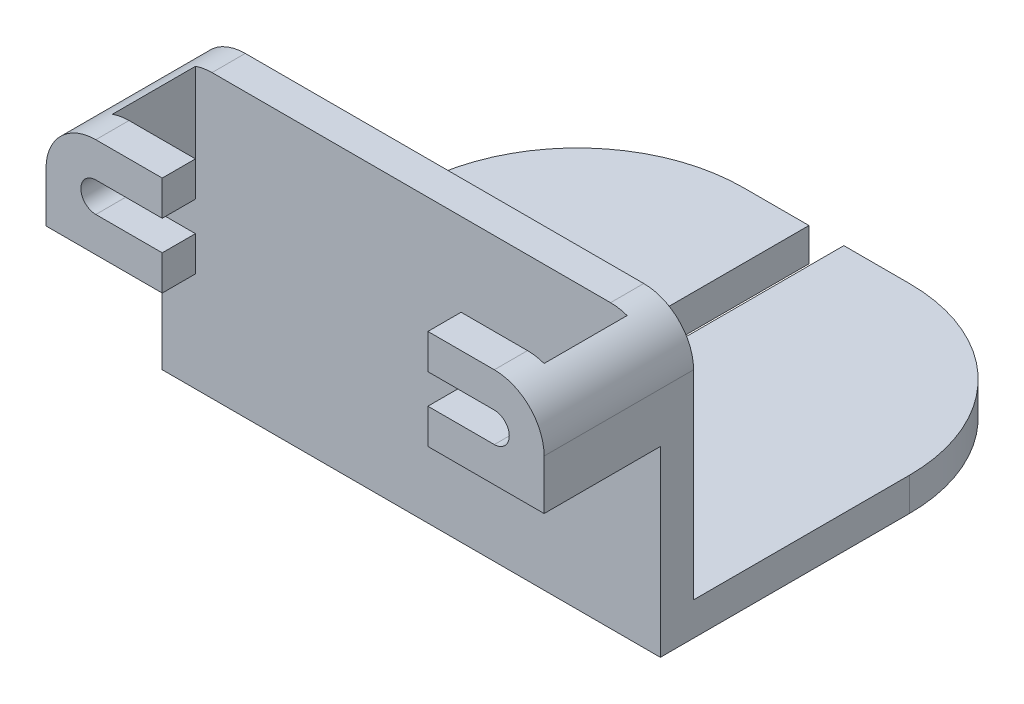
SolidWorks part; units mm, degrees
ref_plane "前视基准面" through (0, 0, 0) normal (0, 0, 1) x (1, 0, 0)
ref_plane "上视基准面" through (0, 0, 0) normal (0, 1, 0) x (1, 0, 0)
ref_plane "右视基准面" through (0, 0, 0) normal (1, 0, 0) x (0, 0, -1)
other "Configuration Table"
sketch "草图1" plane through (0, 0, 0) normal (1, 0, 0) x (0, 0, -1)
  line L1 (0, 0) -> (25, 0)
  line L2 (0, 0) -> (0, 17)
  line L3 (0, 17) -> (2, 17)
  line L4 (25, 0) -> (25, 2)
  line L8 (25, 2) -> (2, 2)
  line L9 (2, 17) -> (2, 2)
  dimension "D1" = 2
  dimension "D2" = 2
  dimension "D3" = 25
  dimension "D4" = 15
extrude "凸台-拉伸1" add sketch "草图1" along normal blind 30
sketch "草图3" plane through (0, 17, 0) normal (0, 1, 0) x (1, 0, 0)
  line L0 (15, 0) -> (15, 9.3774) construction
  line L2 (0, 0) -> (0, -7)
  line L3 (0, -7) -> (7, -7)
  line L4 (7, -7) -> (7, -5)
  line L5 (7, -5) -> (2, -5)
  line L6 (2, -5) -> (2, 0)
  line L7 (30, 0) -> (0, 0) construction
  line L8 (2, 0) -> (0, 0)
  line L9 (28, -5) -> (28, 0)
  line L10 (23, -5) -> (28, -5)
  line L11 (23, -7) -> (23, -5)
  line L12 (30, -7) -> (23, -7)
  line L13 (30, 0) -> (30, -7)
  line L14 (28, 0) -> (30, 0)
  dimension "D1" = 2
  dimension "D2" = 2
  dimension "D3" = 5
  dimension "D4" = 5
extrude "凸台-拉伸2" add sketch "草图3" against normal blind 6
sketch "草图4" plane through (0, 0, 7) normal (0, 0, 1) x (1, 0, 0)
  line L0 (23, 14) -> (33.8566, 14) construction
  line L2 (22.347, 14) -> (27, 14) construction
  line L3 (22.347, 14.9) -> (27, 14.9)
  line L4 (22.347, 13.1) -> (27, 13.1)
  line L5 (15, 17) -> (15, 5.0737) construction
  line L7 (7.653, 14) -> (3, 14) construction
  line L8 (7.653, 14.9) -> (3, 14.9)
  line L9 (7.653, 13.1) -> (3, 13.1)
  line L10 (23, 11) -> (23, 17) construction
  arc A0 (22.347, 14.9) -> (22.347, 13.1) centre (22.347, 14) ccw
  arc A1 (27, 13.1) -> (27, 14.9) centre (27, 14) ccw
  arc A2 (7.653, 14.9) -> (7.653, 13.1) centre (7.653, 14) cw
  arc A3 (3, 13.1) -> (3, 14.9) centre (3, 14) cw
  point P3 (24.6735, 14)
  point P12 (5.3265, 14)
  point P18 (25.9663, 14)
  point P19 (24.6958, 14)
  point P20 (24.8072, 14)
  point P21 (0, 0)
  point P22 (25.2976, 14)
  point P23 (24.8295, 14)
  point P26 (24.6735, 14)
  dimension "D1" = 0.9
  dimension "D2" = 4
  dimension "D3" = 4.653
extrude "切除-拉伸1" cut sketch "草图4" against normal blind 6
sketch "草图5" plane through (0, 2, 0) normal (0, 1, 0) x (1, 0, 0)
  line L0 (15, 25) -> (15, 9.4461) construction
  line L2 (15, 25.5291) -> (15, 11.5291) construction
  line L3 (16.05, 25.5291) -> (16.05, 11.5291)
  line L4 (13.95, 25.5291) -> (13.95, 11.5291)
  line L5 (30, 25) -> (0, 25) construction
  arc A0 (16.05, 25.5291) -> (13.95, 25.5291) centre (15, 25.5291) ccw
  arc A1 (13.95, 11.5291) -> (16.05, 11.5291) centre (15, 11.5291) ccw
  point P3 (15, 18.5291)
  point P9 (15, 14.3418)
  point P10 (15, 18.5291)
  point P11 (0, 0)
  dimension "D1" = 1.05
  dimension "D2" = 14
  dimension "D3" = 13.4709
extrude "切除-拉伸2" cut sketch "草图5" against normal blind 6
fillet "圆角1" radius 10 2 edges at (0, 1, -25) (30, 1, -25)
fillet "圆角2" radius 3 2 edges at (30, 17, 2.5) (0, 17, 2.5)
